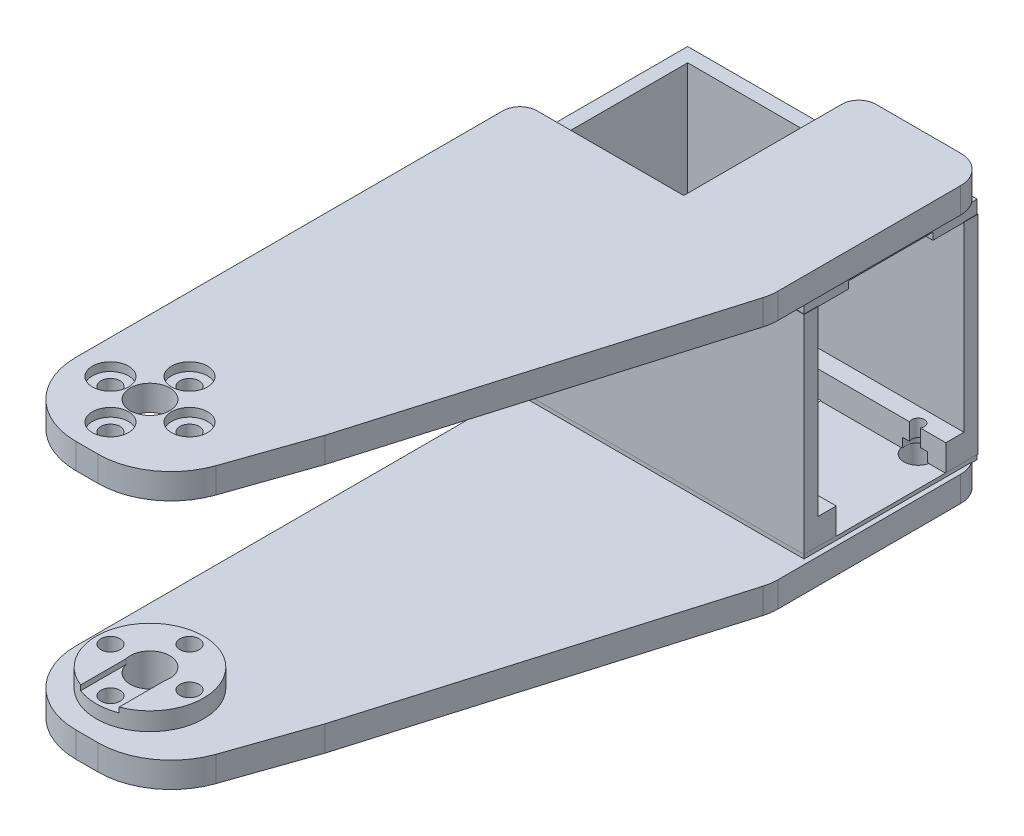
SolidWorks part; units mm, degrees
ref_plane "Front Plane" through (0, 0, 0) normal (0, 0, 1) x (1, 0, 0)
ref_plane "Top Plane" through (0, 0, 0) normal (0, 1, 0) x (1, 0, 0)
ref_plane "Right Plane" through (0, 0, 0) normal (1, 0, 0) x (0, 0, -1)
ref_plane "PY_p18_800" through (0, 18.8, 0) normal (0, 1, 0) x (1, 0, 0)
sketch "S_prism1" plane through (0, 18.8, 0) normal (0, 1, 0) x (1, 0, 0)
  line L0 (-0.1, -13) -> (3.8289, -13)
  line L1 (16.0129, -4.3379) -> (21, 10)
  line L2 (21, 10) -> (38.6729, 69.8916)
  line L3 (39, 72.1557) -> (39, 104.5)
  line L4 (34, 109.5) -> (19, 109.5)
  line L5 (16, 106.5) -> (16, 78.5)
  line L6 (16, 78.5) -> (-10, 78.5)
  line L7 (-13, 75.5) -> (-13, -0.1)
  arc A0 (-13, -0.1) -> (-0.1, -13) centre (-0.1001, -0.1001) ccw
  arc A1 (3.8289, -13) -> (16.0129, -4.3379) centre (3.8289, -0.1) ccw
  arc A2 (38.6729, 69.8916) -> (39, 72.1557) centre (31.0004, 72.1557) ccw
  arc A3 (39, 104.5) -> (34, 109.5) centre (33.9999, 104.4999) ccw
  arc A4 (19, 109.5) -> (16, 106.5) centre (19.0001, 106.4999) ccw
  arc A5 (-10, 78.5) -> (-13, 75.5) centre (-9.9999, 75.4999) ccw
extrude "Boss_1" add sketch "S_prism1" along normal blind 4.5
ref_plane "PY_m20_950" through (0, -20.95, 0) normal (0, 1, 0) x (1, 0, 0)
sketch "S_cyl2" plane through (0, -20.95, 0) normal (0, 1, 0) x (1, 0, 0)
  circle A0 centre (0, 0) radius 9.5
  dimension "D1_S_cyl2" = 19
extrude "Boss_2" add sketch "S_cyl2" along normal blind 3.2
ref_plane "PY_m25_450" through (0, -25.45, 0) normal (0, 1, 0) x (1, 0, 0)
sketch "S_prism3" plane through (0, -25.45, 0) normal (0, 1, 0) x (1, 0, 0)
  line L0 (-0.1, -13) -> (3.8289, -13)
  line L1 (16.0129, -4.3379) -> (21, 10)
  line L2 (21, 10) -> (38.6729, 69.8916)
  line L3 (39, 72.1557) -> (39, 104.5)
  line L4 (34, 109.5) -> (19, 109.5)
  line L5 (16, 106.5) -> (16, 78.5)
  line L6 (16, 78.5) -> (-10, 78.5)
  line L7 (-13, 75.5) -> (-13, -0.1)
  arc A0 (-13, -0.1) -> (-0.1, -13) centre (-0.1001, -0.1001) ccw
  arc A1 (3.8289, -13) -> (16.0129, -4.3379) centre (3.8289, -0.1) ccw
  arc A2 (38.6729, 69.8916) -> (39, 72.1557) centre (31.0004, 72.1557) ccw
  arc A3 (39, 104.5) -> (34, 109.5) centre (33.9999, 104.4999) ccw
  arc A4 (19, 109.5) -> (16, 106.5) centre (19.0001, 106.4999) ccw
  arc A5 (-10, 78.5) -> (-13, 75.5) centre (-9.9999, 75.4999) ccw
extrude "Boss_3" add sketch "S_prism3" along normal blind 4.5
ref_plane "PZ_m108_400" through (0, 0, -108.4) normal (0, 0, 1) x (1, 0, 0)
sketch "S_box4" plane through (0, 0, -108.4) normal (0, 0, 1) x (1, 0, 0)
  line L0 (-13.2, -20.2) -> (-10.7, -20.2)
  line L1 (-10.7, -20.2) -> (-10.7, 16.6)
  line L2 (-10.7, 16.6) -> (-13.2, 16.6)
  line L3 (-13.2, 16.6) -> (-13.2, -20.2)
  dimension "P1" = 13.2
  dimension "P2" = 20.2
  dimension "P3" = 10.7
  dimension "P4" = 20.2
  dimension "P5" = 10.7
  dimension "P6" = 16.6
  dimension "P7" = 13.2
  dimension "P8" = 16.6
extrude "Boss_4" add sketch "S_box4" along normal blind 30.8
sketch "S_box5" plane through (0, 0, -108.4) normal (0, 0, 1) x (1, 0, 0)
  line L0 (-13.2, -20.2) -> (38.2, -20.2)
  line L1 (38.2, -20.2) -> (38.2, 16.6)
  line L2 (38.2, 16.6) -> (-13.2, 16.6)
  line L3 (-13.2, 16.6) -> (-13.2, -20.2)
  dimension "P1" = 13.2
  dimension "P2" = 20.2
  dimension "P3" = 38.2
  dimension "P4" = 20.2
  dimension "P5" = 38.2
  dimension "P6" = 16.6
  dimension "P7" = 13.2
  dimension "P8" = 16.6
extrude "Boss_5" add sketch "S_box5" along normal blind 2.5
ref_plane "PZ_m80_100" through (0, 0, -80.1) normal (0, 0, 1) x (1, 0, 0)
sketch "S_box6" plane through (0, 0, -80.1) normal (0, 0, 1) x (1, 0, 0)
  line L0 (-13.2, -20.2) -> (38.2, -20.2)
  line L1 (38.2, -20.2) -> (38.2, 16.6)
  line L2 (38.2, 16.6) -> (-13.2, 16.6)
  line L3 (-13.2, 16.6) -> (-13.2, -20.2)
  dimension "P1" = 13.2
  dimension "P2" = 20.2
  dimension "P3" = 38.2
  dimension "P4" = 20.2
  dimension "P5" = 38.2
  dimension "P6" = 16.6
  dimension "P7" = 13.2
  dimension "P8" = 16.6
extrude "Boss_6" add sketch "S_box6" along normal blind 2.5
sketch "S_box7" plane through (0, 0, -108.4) normal (0, 0, 1) x (1, 0, 0)
  line L0 (-13.2, -20.2) -> (38.2, -20.2)
  line L1 (38.2, -20.2) -> (38.2, -15.6)
  line L2 (38.2, -15.6) -> (-13.2, -15.6)
  line L3 (-13.2, -15.6) -> (-13.2, -20.2)
  dimension "P1" = 13.2
  dimension "P2" = 20.2
  dimension "P3" = 38.2
  dimension "P4" = 20.2
  dimension "P5" = 38.2
  dimension "P6" = 15.6
  dimension "P7" = 13.2
  dimension "P8" = 15.6
extrude "Boss_7" add sketch "S_box7" along normal blind 30.8
ref_plane "PZ_m108_330" through (0, 0, -108.33) normal (0, 0, 1) x (1, 0, 0)
sketch "S_box8" plane through (0, 0, -108.33) normal (0, 0, 1) x (1, 0, 0)
  line L0 (16, 16.5) -> (38.13, 16.5)
  line L1 (38.13, 16.5) -> (38.13, 18.9)
  line L2 (38.13, 18.9) -> (16, 18.9)
  line L3 (16, 18.9) -> (16, 16.5)
  dimension "P1" = 16
  dimension "P2" = 16.5
  dimension "P3" = 38.13
  dimension "P4" = 16.5
  dimension "P5" = 38.13
  dimension "P6" = 18.9
  dimension "P7" = 16
  dimension "P8" = 18.9
extrude "Boss_8" add sketch "S_box8" along normal blind 30.66
ref_plane "PZ_m79_500" through (0, 0, -79.5) normal (0, 0, 1) x (1, 0, 0)
sketch "S_box9" plane through (0, 0, -79.5) normal (0, 0, 1) x (1, 0, 0)
  line L0 (-13.13, 16.5) -> (16.03, 16.5)
  line L1 (16.03, 16.5) -> (16.03, 18.9)
  line L2 (16.03, 18.9) -> (-13.13, 18.9)
  line L3 (-13.13, 18.9) -> (-13.13, 16.5)
  dimension "P1" = 13.13
  dimension "P2" = 16.5
  dimension "P3" = 16.03
  dimension "P4" = 16.5
  dimension "P5" = 16.03
  dimension "P6" = 18.9
  dimension "P7" = 13.13
  dimension "P8" = 18.9
extrude "Boss_9" add sketch "S_box9" along normal blind 1.83
sketch "S_box10" plane through (0, 0, -108.33) normal (0, 0, 1) x (1, 0, 0)
  line L0 (16, -21.05) -> (38.13, -21.05)
  line L1 (38.13, -21.05) -> (38.13, -20.1)
  line L2 (38.13, -20.1) -> (16, -20.1)
  line L3 (16, -20.1) -> (16, -21.05)
  dimension "P1" = 16
  dimension "P2" = 21.05
  dimension "P3" = 38.13
  dimension "P4" = 21.05
  dimension "P5" = 38.13
  dimension "P6" = 20.1
  dimension "P7" = 16
  dimension "P8" = 20.1
extrude "Boss_10" add sketch "S_box10" along normal blind 30.66
sketch "S_box11" plane through (0, 0, -79.5) normal (0, 0, 1) x (1, 0, 0)
  line L0 (-13.13, -21.05) -> (16.03, -21.05)
  line L1 (16.03, -21.05) -> (16.03, -20.1)
  line L2 (16.03, -20.1) -> (-13.13, -20.1)
  line L3 (-13.13, -20.1) -> (-13.13, -21.05)
  dimension "P1" = 13.13
  dimension "P2" = 21.05
  dimension "P3" = 16.03
  dimension "P4" = 21.05
  dimension "P5" = 16.03
  dimension "P6" = 20.1
  dimension "P7" = 13.13
  dimension "P8" = 20.1
extrude "Boss_11" add sketch "S_box11" along normal blind 1.83
ref_plane "PY_p18_700" through (0, 18.7, 0) normal (0, 1, 0) x (1, 0, 0)
sketch "S_hole12" plane through (0, 18.7, 0) normal (0, 1, 0) x (1, 0, 0)
  circle A0 centre (0, 0) radius 3.5
  dimension "D1_S_hole12" = 7
extrude "Hole_12" cut sketch "S_hole12" along normal blind 4.7
sketch "S_hole13" plane through (0, 18.7, 0) normal (0, 1, 0) x (1, 0, 0)
  circle A0 centre (7, 0) radius 1.7
  dimension "D1_S_hole13" = 3.4
  dimension "P2" = 7
extrude "Hole_13" cut sketch "S_hole13" along normal blind 4.7
sketch "S_hole14" plane through (0, 18.7, 0) normal (0, 1, 0) x (1, 0, 0)
  circle A0 centre (0, -7) radius 1.7
  dimension "D1_S_hole14" = 3.4
  dimension "P2" = 7
extrude "Hole_14" cut sketch "S_hole14" along normal blind 4.7
sketch "S_hole15" plane through (0, 18.7, 0) normal (0, 1, 0) x (1, 0, 0)
  circle A0 centre (-7, 0) radius 1.7
  dimension "D1_S_hole15" = 3.4
  dimension "P2" = 7
extrude "Hole_15" cut sketch "S_hole15" along normal blind 4.7
sketch "S_hole16" plane through (0, 18.7, 0) normal (0, 1, 0) x (1, 0, 0)
  circle A0 centre (0, 7) radius 1.7
  dimension "D1_S_hole16" = 3.4
  dimension "P2" = 7
extrude "Hole_16" cut sketch "S_hole16" along normal blind 4.7
ref_plane "PY_p21_800" through (0, 21.8, 0) normal (0, 1, 0) x (1, 0, 0)
sketch "S_hole17" plane through (0, 21.8, 0) normal (0, 1, 0) x (1, 0, 0)
  circle A0 centre (7, 0) radius 3.2
  dimension "D1_S_hole17" = 6.4
  dimension "P2" = 7
extrude "Hole_17" cut sketch "S_hole17" along normal blind 1.6
sketch "S_hole18" plane through (0, 21.8, 0) normal (0, 1, 0) x (1, 0, 0)
  circle A0 centre (0, -7) radius 3.2
  dimension "D1_S_hole18" = 6.4
  dimension "P2" = 7
extrude "Hole_18" cut sketch "S_hole18" along normal blind 1.6
sketch "S_hole19" plane through (0, 21.8, 0) normal (0, 1, 0) x (1, 0, 0)
  circle A0 centre (-7, 0) radius 3.2
  dimension "D1_S_hole19" = 6.4
  dimension "P2" = 7
extrude "Hole_19" cut sketch "S_hole19" along normal blind 1.6
sketch "S_hole20" plane through (0, 21.8, 0) normal (0, 1, 0) x (1, 0, 0)
  circle A0 centre (0, 7) radius 3.2
  dimension "D1_S_hole20" = 6.4
  dimension "P2" = 7
extrude "Hole_20" cut sketch "S_hole20" along normal blind 1.6
ref_plane "PY_m25_550" through (0, -25.55, 0) normal (0, 1, 0) x (1, 0, 0)
sketch "S_hole21" plane through (0, -25.55, 0) normal (0, 1, 0) x (1, 0, 0)
  circle A0 centre (0, 0) radius 3.5
  dimension "D1_S_hole21" = 7
extrude "Hole_21" cut sketch "S_hole21" along normal blind 7.9
sketch "S_hole22" plane through (0, -25.55, 0) normal (0, 1, 0) x (1, 0, 0)
  circle A0 centre (7, 0) radius 1.7
  dimension "D1_S_hole22" = 3.4
  dimension "P2" = 7
extrude "Hole_22" cut sketch "S_hole22" along normal blind 7.9
sketch "S_hole23" plane through (0, -25.55, 0) normal (0, 1, 0) x (1, 0, 0)
  circle A0 centre (0, -7) radius 1.7
  dimension "D1_S_hole23" = 3.4
  dimension "P2" = 7
extrude "Hole_23" cut sketch "S_hole23" along normal blind 7.9
sketch "S_hole24" plane through (0, -25.55, 0) normal (0, 1, 0) x (1, 0, 0)
  circle A0 centre (-7, 0) radius 1.7
  dimension "D1_S_hole24" = 3.4
  dimension "P2" = 7
extrude "Hole_24" cut sketch "S_hole24" along normal blind 7.9
sketch "S_hole25" plane through (0, -25.55, 0) normal (0, 1, 0) x (1, 0, 0)
  circle A0 centre (0, 7) radius 1.7
  dimension "D1_S_hole25" = 3.4
  dimension "P2" = 7
extrude "Hole_25" cut sketch "S_hole25" along normal blind 7.9
sketch "S_hole26" plane through (0, -25.55, 0) normal (0, 1, 0) x (1, 0, 0)
  circle A0 centre (7, 0) radius 3.2
  dimension "D1_S_hole26" = 6.4
  dimension "P2" = 7
extrude "Hole_26" cut sketch "S_hole26" along normal blind 2.1
sketch "S_hole27" plane through (0, -25.55, 0) normal (0, 1, 0) x (1, 0, 0)
  circle A0 centre (0, -7) radius 3.2
  dimension "D1_S_hole27" = 6.4
  dimension "P2" = 7
extrude "Hole_27" cut sketch "S_hole27" along normal blind 2.1
sketch "S_hole28" plane through (0, -25.55, 0) normal (0, 1, 0) x (1, 0, 0)
  circle A0 centre (-7, 0) radius 3.2
  dimension "D1_S_hole28" = 6.4
  dimension "P2" = 7
extrude "Hole_28" cut sketch "S_hole28" along normal blind 2.1
sketch "S_hole29" plane through (0, -25.55, 0) normal (0, 1, 0) x (1, 0, 0)
  circle A0 centre (0, 7) radius 3.2
  dimension "D1_S_hole29" = 6.4
  dimension "P2" = 7
extrude "Hole_29" cut sketch "S_hole29" along normal blind 2.1
sketch "S_cut30" plane through (0, 0, 0) normal (0, 0, 1) x (1, 0, 0)
  line L0 (-3.4, -18.65) -> (3.4, -18.65)
  line L1 (3.4, -18.65) -> (3.4, -17.65)
  line L2 (3.4, -17.65) -> (-3.4, -17.65)
  line L3 (-3.4, -17.65) -> (-3.4, -18.65)
  dimension "P1" = 3.4
  dimension "P2" = 18.65
  dimension "P3" = 3.4
  dimension "P4" = 18.65
  dimension "P5" = 3.4
  dimension "P6" = 17.65
  dimension "P7" = 3.4
  dimension "P8" = 17.65
extrude "Pocket_30" cut sketch "S_cut30" along normal blind 10
ref_plane "PY_m20_300" through (0, -20.3, 0) normal (0, 1, 0) x (1, 0, 0)
sketch "S_hole31" plane through (0, -20.3, 0) normal (0, 1, 0) x (1, 0, 0)
  circle A0 centre (0, 93) radius 10.5
  dimension "D1_S_hole31" = 21
  dimension "P2" = 93
extrude "Hole_31" cut sketch "S_hole31" along normal blind 4.8
ref_plane "PZ_m102_700" through (0, 0, -102.7) normal (0, 0, 1) x (1, 0, 0)
sketch "S_cut32" plane through (0, 0, -102.7) normal (0, 0, 1) x (1, 0, 0)
  line L0 (10.9, -20.3) -> (30.4, -20.3)
  line L1 (30.4, -20.3) -> (30.4, -15.55)
  line L2 (30.4, -15.55) -> (10.9, -15.55)
  line L3 (10.9, -15.55) -> (10.9, -20.3)
  dimension "P1" = 10.9
  dimension "P2" = 20.3
  dimension "P3" = 30.4
  dimension "P4" = 20.3
  dimension "P5" = 30.4
  dimension "P6" = 15.55
  dimension "P7" = 10.9
  dimension "P8" = 15.55
extrude "Pocket_32" cut sketch "S_cut32" along normal blind 19.4
sketch "S_cut33" plane through (0, 0, -102.7) normal (0, 0, 1) x (1, 0, 0)
  line L0 (30.4, -20.3) -> (38.7, -20.3)
  line L1 (38.7, -20.3) -> (38.7, -15.55)
  line L2 (38.7, -15.55) -> (30.4, -15.55)
  line L3 (30.4, -15.55) -> (30.4, -20.3)
  dimension "P1" = 30.4
  dimension "P2" = 20.3
  dimension "P3" = 38.7
  dimension "P4" = 20.3
  dimension "P5" = 38.7
  dimension "P6" = 15.55
  dimension "P7" = 30.4
  dimension "P8" = 15.55
extrude "Pocket_33" cut sketch "S_cut33" along normal blind 19.4
ref_plane "PZ_m96_500" through (0, 0, -96.5) normal (0, 0, 1) x (1, 0, 0)
sketch "S_cut34" plane through (0, 0, -96.5) normal (0, 0, 1) x (1, 0, 0)
  line L0 (0, -20.3) -> (11, -20.3)
  line L1 (11, -20.3) -> (11, -15.55)
  line L2 (11, -15.55) -> (0, -15.55)
  line L3 (0, -15.55) -> (0, -20.3)
  dimension "P1" = 20.3
  dimension "P2" = 11
  dimension "P3" = 20.3
  dimension "P4" = 11
  dimension "P5" = 15.55
  dimension "P6" = 15.55
extrude "Pocket_34" cut sketch "S_cut34" along normal blind 7
ref_plane "PZ_m108_900" through (0, 0, -108.9) normal (0, 0, 1) x (1, 0, 0)
sketch "S_cut35" plane through (0, 0, -108.9) normal (0, 0, 1) x (1, 0, 0)
  line L0 (-10, -20.4) -> (10, -20.4)
  line L1 (10, -20.4) -> (10, -17.5)
  line L2 (10, -17.5) -> (-10, -17.5)
  line L3 (-10, -17.5) -> (-10, -20.4)
  dimension "P1" = 10
  dimension "P2" = 20.4
  dimension "P3" = 10
  dimension "P4" = 20.4
  dimension "P5" = 10
  dimension "P6" = 17.5
  dimension "P7" = 10
  dimension "P8" = 17.5
extrude "Pocket_35" cut sketch "S_cut35" along normal blind 15.9
sketch "S_hole36" plane through (0, -20.3, 0) normal (0, 1, 0) x (1, 0, 0)
  circle A0 centre (8.3, 82.75) radius 1.1
  dimension "D1_S_hole36" = 2.2
  dimension "P2" = 8.3
  dimension "P3" = 82.75
extrude "Hole_36" cut sketch "S_hole36" along normal blind 4.8
sketch "S_hole37" plane through (0, -20.3, 0) normal (0, 1, 0) x (1, 0, 0)
  circle A0 centre (8.3, 82.75) radius 2.3
  dimension "D1_S_hole37" = 4.6
  dimension "P2" = 8.3
  dimension "P3" = 82.75
extrude "Hole_37" cut sketch "S_hole37" along normal blind 1.7
sketch "S_hole38" plane through (0, -20.3, 0) normal (0, 1, 0) x (1, 0, 0)
  circle A0 centre (32.75, 103.25) radius 1.1
  dimension "D1_S_hole38" = 2.2
  dimension "P2" = 32.75
  dimension "P3" = 103.25
extrude "Hole_38" cut sketch "S_hole38" along normal blind 4.8
sketch "S_hole39" plane through (0, -20.3, 0) normal (0, 1, 0) x (1, 0, 0)
  circle A0 centre (32.75, 103.25) radius 2.3
  dimension "D1_S_hole39" = 4.6
  dimension "P2" = 32.75
  dimension "P3" = 103.25
extrude "Hole_39" cut sketch "S_hole39" along normal blind 1.7
sketch "S_hole40" plane through (0, -20.3, 0) normal (0, 1, 0) x (1, 0, 0)
  circle A0 centre (32.75, 82.75) radius 1.1
  dimension "D1_S_hole40" = 2.2
  dimension "P2" = 32.75
  dimension "P3" = 82.75
extrude "Hole_40" cut sketch "S_hole40" along normal blind 4.8
sketch "S_hole41" plane through (0, -20.3, 0) normal (0, 1, 0) x (1, 0, 0)
  circle A0 centre (32.75, 82.75) radius 2.3
  dimension "D1_S_hole41" = 4.6
  dimension "P2" = 32.75
  dimension "P3" = 82.75
extrude "Hole_41" cut sketch "S_hole41" along normal blind 1.7
ref_plane "PZ_m100_500" through (0, 0, -100.5) normal (0, 0, 1) x (1, 0, 0)
sketch "S_cut42" plane through (0, 0, -100.5) normal (0, 0, 1) x (1, 0, 0)
  line L0 (8.1, 16.2) -> (38.7, 16.2)
  line L1 (38.7, 16.2) -> (38.7, 17.75)
  line L2 (38.7, 17.75) -> (8.1, 17.75)
  line L3 (8.1, 17.75) -> (8.1, 16.2)
  dimension "P1" = 8.1
  dimension "P2" = 16.2
  dimension "P3" = 38.7
  dimension "P4" = 16.2
  dimension "P5" = 38.7
  dimension "P6" = 17.75
  dimension "P7" = 8.1
  dimension "P8" = 17.75
extrude "Pocket_42" cut sketch "S_cut42" along normal blind 15
sketch "S_hole43" plane through (0, -25.55, 0) normal (0, 1, 0) x (1, 0, 0)
  circle A0 centre (32.75, 103.25) radius 2.5
  dimension "D1_S_hole43" = 5
  dimension "P2" = 32.75
  dimension "P3" = 103.25
extrude "Hole_43" cut sketch "S_hole43" along normal blind 5.3
sketch "S_hole44" plane through (0, -25.55, 0) normal (0, 1, 0) x (1, 0, 0)
  circle A0 centre (32.75, 82.75) radius 2.5
  dimension "D1_S_hole44" = 5
  dimension "P2" = 32.75
  dimension "P3" = 82.75
extrude "Hole_44" cut sketch "S_hole44" along normal blind 5.3
ref_plane "PY_m20_400" through (0, -20.4, 0) normal (0, 1, 0) x (1, 0, 0)
sketch "S_pcut45" plane through (0, -20.4, 0) normal (0, 1, 0) x (1, 0, 0)
  line L0 (0.5, 109.308) -> (0.5, 113)
  line L1 (0.5, 113) -> (-20, 113)
  line L2 (-20, 113) -> (-20, 93)
  line L3 (-20, 93) -> (-16.3, 93)
  arc A0 (-16.3, 93) -> (0.5, 109.308) centre (0.0258, 92.9891) cw
extrude "Cut_45" cut sketch "S_pcut45" along normal blind 4.9
ref_plane "PY_m15_600" through (0, -15.6, 0) normal (0, 1, 0) x (1, 0, 0)
sketch "S_pcut46" plane through (0, -15.6, 0) normal (0, 1, 0) x (1, 0, 0)
  line L0 (0.5, 111.508) -> (0.5, 113)
  line L1 (0.5, 113) -> (-20, 113)
  line L2 (-20, 113) -> (-20, 93)
  line L3 (-20, 93) -> (-18.5, 93)
  arc A0 (-18.5, 93) -> (0.5, 111.508) centre (0.0245, 92.9896) cw
extrude "Cut_46" cut sketch "S_pcut46" along normal blind 32
equation "\"plate_t\" = 3"
equation "\"clearance\" = 0.5"
